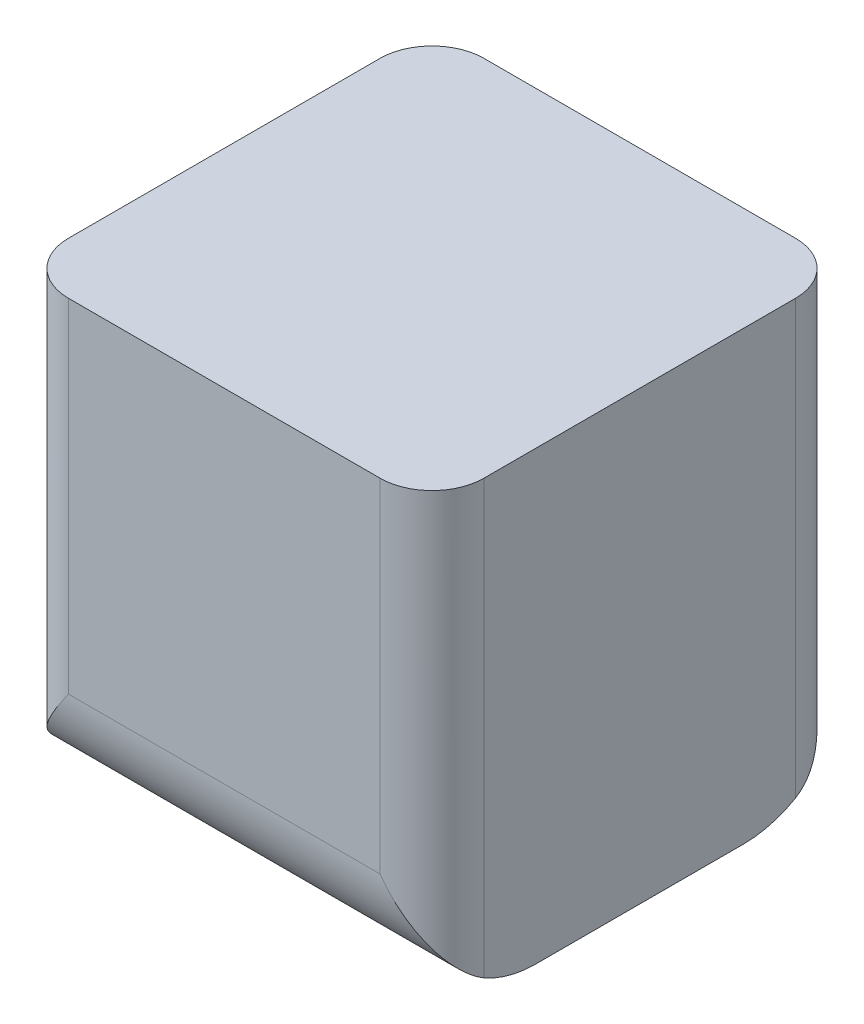
SolidWorks part; units mm, degrees
material "1060 Alloy"
ref_plane "Front Plane" through (0, 0, 0) normal (0, 0, 1) x (1, 0, 0)
ref_plane "Top Plane" through (0, 0, 0) normal (0, 1, 0) x (1, 0, 0)
ref_plane "Right Plane" through (0, 0, 0) normal (1, 0, 0) x (0, 0, -1)
sketch "Sketch1" plane through (0, 0, 0) normal (0, 0, 1) x (1, 0, 0)
  line L10 (-2, 2) -> (-2, 6) construction
  line L11 (-2, 6.244) -> (2, 6.244)
  line L12 (-2, 6.244) -> (-2, 1.944)
  line L13 (-2, 1.944) -> (2, 1.944)
  line L14 (2, 6.244) -> (2, 1.944)
  line L15 (-1.8358, 6.244) -> (2.2782, 6.244) construction
  dimension "D1" = 4
  dimension "D2" = 4.3
extrude "Boss-Extrude1" add sketch "Sketch1" along normal mid plane 4
fillet "Fillet1" radius 0.5
fillet "Fillet2" radius 1
